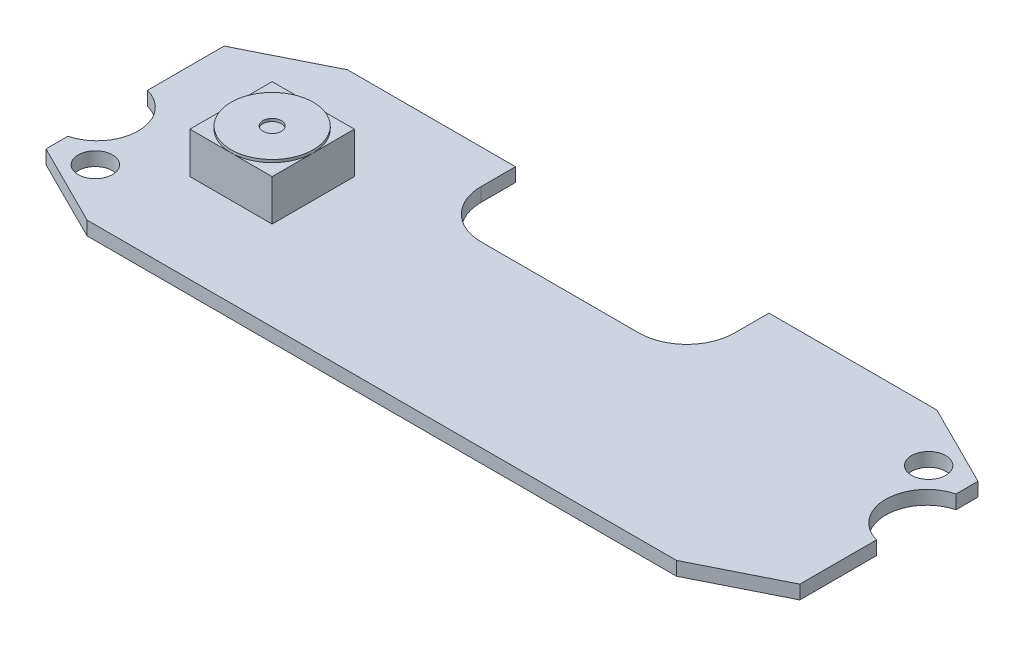
SolidWorks part; units mm, degrees
ref_plane "Front" through (0, 0, 0) normal (0, 0, 1) x (1, 0, 0)
ref_plane "Top" through (0, 0, 0) normal (0, 1, 0) x (1, 0, 0)
ref_plane "Right" through (0, 0, 0) normal (1, 0, 0) x (0, 0, -1)
sketch "草圖1" plane through (0, 0, 0) normal (0, 1, 0) x (1, 0, 0)
  line L0 (-37.8777, -5.205) -> (-26.0392, -5.0914) construction
  line L1 (-40.7273, 0) -> (40.7273, 0) construction
  line L2 (0, -25.447) -> (0, 25.447) construction
  line L3 (-21.5, -9.5) -> (21.5, -9.5)
  line L4 (-27.5, -6.5) -> (-27.5, -4.9)
  line L5 (-21.5, 9.5) -> (-9.25, 9.5)
  line L6 (27.5, -6.5) -> (27.5, -0.9)
  line L7 (-21.5, -9.5) -> (21.5, 9.5) construction
  line L8 (-21.5, 9.5) -> (21.5, -9.5) construction
  line L9 (-21.5, 9.5) -> (-27.5, 6.5)
  line L10 (-21.5, -9.5) -> (-27.5, -6.5)
  line L11 (21.5, 9.5) -> (27.5, 6.5)
  line L12 (21.5, -9.5) -> (27.5, -6.5)
  line L13 (27.5, 4.9) -> (27.5, 6.5)
  line L14 (-27.5, 0.9) -> (-27.5, 6.5)
  line L15 (9.25, 9.5) -> (21.5, 9.5)
  line L16 (-5.75, 3.5) -> (5.75, 3.5)
  line L17 (-9.25, 7) -> (-9.25, 9.5)
  line L18 (-24.7, -5.7) -> (24.7, 5.7) construction
  line L19 (9.25, 7) -> (9.25, 9.5)
  line L20 (-9.25, 3.5) -> (9.25, 9.5) construction
  line L21 (-9.25, 9.5) -> (9.25, 3.5) construction
  line L23 (-20.5, -3) -> (-14.5, -3)
  line L24 (-20.5, -3) -> (-20.5, 3)
  line L25 (-20.5, 3) -> (-14.5, 3)
  line L26 (-14.5, -3) -> (-14.5, 3)
  line L27 (-20.5, -3) -> (-14.5, 3) construction
  line L28 (-20.5, 3) -> (-14.5, -3) construction
  arc A0 (-27.5, 0.9) -> (-27.5, -4.9) centre (-28.2681, -2) cw
  circle A1 centre (-17.5, 0) radius 3
  circle A2 centre (-17.5, 0) radius 0.675
  arc A3 (5.75, 3.5) -> (9.25, 7) centre (5.75, 7) ccw
  arc A4 (27.5, -0.9) -> (27.5, 4.9) centre (28.2681, 2) cw
  arc A5 (-5.75, 3.5) -> (-9.25, 7) centre (-5.75, 7) cw
  arc A6 (-0.9, -27.5) -> (4.9, -27.5) centre (2, -28.2681) cw [skipped]
  arc A7 (0.9, 27.5) -> (-4.9, 27.5) centre (-2, 28.2681) cw [skipped]
  circle A8 centre (24.7, 5.7) radius 1.25
  circle A9 centre (-24.7, -5.7) radius 1.25
  point P4 (0, 0)
  point P6 (0, 6.5)
  point P11 (0, 0)
  point P14 (0, 0)
  point P34 (0, 0)
  point P46 (0, 0)
  point P56 (0, 0)
  dimension "D6" = 6
  dimension "D7" = 1.35
  dimension "D8" = 3
  dimension "D14" = 3.5
  dimension "D15" = 2.5
  dimension "D1" = 55
  dimension "D2" = 19
  dimension "D3" = 13
  dimension "D4" = 43
  dimension "D5" = 17.5
  dimension "D9" = 5.8
  dimension "D10" = 4.5
  dimension "D12" = 6
  dimension "D13" = 18.5
  dimension "D16" = 5.7
  dimension "D17" = 24.7
  dimension "D11" = 4
  dimension "D18" = 2
extrude "填料-伸長1" add sketch "草圖1" along normal blind 1 contours L16 A5 L17 L5 L9 L14 A0 L4 L10 L3 L12 L6 A4 L13 L11 L15 L19 A3 A9 A8 A1 | L26 L25 L24 L23 region at (0.7515, 0, 0.8338)
extrude "填料-伸長2" add sketch "草圖1<3>" along normal blind 4 contours A1 A2 | A1 L23 L26 | A1 L24 L23 | L24 L25 L26 L23 region at (-19.8299, 0, 2.3299) region at (-15.1701, 0, 2.3299) region at (-19.5613, 0, 2.0613)
sketch "草圖1<3>" plane through (0, 0, 0) normal (0, 1, 0) x (1, 0, 0) same geometry as "草圖1"
extrude "填料-伸長5" add sketch "草圖1<4>" along normal blind 0.2 from offset 4 contours A1 A2 region at (-19.5613, 0, 2.0613)
sketch "草圖1<4>" plane through (0, 0, 0) normal (0, 1, 0) x (1, 0, 0) same geometry as "草圖1"
